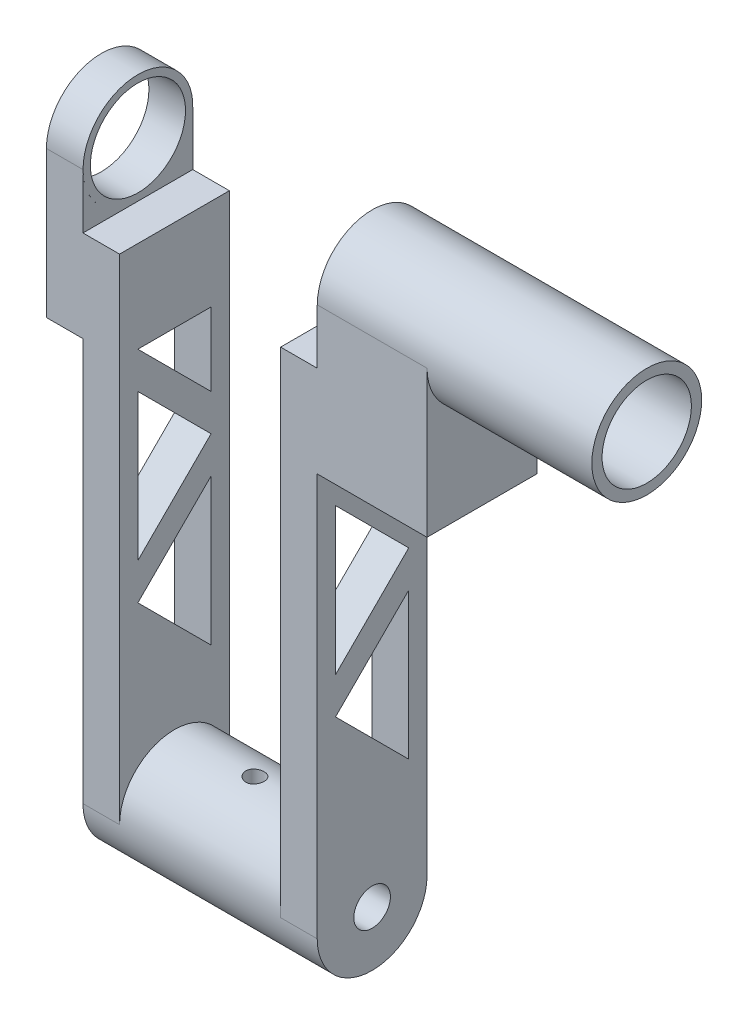
SolidWorks part; units mm, degrees
ref_plane "Alzado" through (0, 0, 0) normal (0, 0, 1) x (1, 0, 0)
ref_plane "Planta" through (0, 0, 0) normal (0, 1, 0) x (1, 0, 0)
ref_plane "Vista lateral" through (0, 0, 0) normal (1, 0, 0) x (0, 0, -1)
sketch "Croquis2" plane through (0, 0, 0) normal (1, 0, 0) x (0, 0, -1)
  line L0 (15, 0) -> (15, 150)
  line L1 (-15, 0) -> (-15, 150)
  line L2 (-15, 150) -> (15, 150) construction
  circle A0 centre (0, 0) radius 5
  arc A1 (-15, 0) -> (15, 0) centre (0, 0) ccw
  arc A2 (15, 150) -> (-15, 150) centre (0, 150) ccw
  circle A3 centre (0, 150) radius 5
extrude "Saliente-Extruir2" add sketch "Croquis2" along normal blind 64
shell "Vaciado1" thickness 10 removed face at (32, -7.5, 0) removed face at (32, 75, -15) removed face at (32, 75, 15)
sketch "Croquis3" plane through (0, 0, 0) normal (0, 1, 0) x (1, 0, 0)
  line L0 (32, 15) -> (32, -15) construction
  line L1 (54, 15) -> (10, 15) construction
  line L2 (10, -15) -> (54, -15) construction
  circle A0 centre (32, 0) radius 2.5
extrude "Cortar-Extruir1" cut sketch "Croquis3" against normal blind 36 and the other way blind 195
sketch "Croquis4" plane through (64, 0, 0) normal (1, 0, 0) x (0, 0, -1)
  line L0 (-15, 130) -> (-10, 130)
  line L1 (-15, 150) -> (-15, 0) construction
  line L2 (-15, 130) -> (15, 130)
  line L3 (15, 0) -> (15, 150) construction
  line L4 (15, 130) -> (10, 130)
  line L5 (10, 130) -> (10, 20)
  line L6 (-15, 20) -> (15, 20)
  line L7 (-15, 20) -> (-15, 130)
  line L8 (-15, 130) -> (15, 130)
  line L9 (15, 20) -> (15, 130)
  line L10 (-10, 130) -> (-10, 20)
  line L11 (10, 130) -> (-10, 110)
  line L12 (-10, 110) -> (10, 90)
extrude "Cortar-Extruir2" cut sketch "Croquis4" against normal blind 90 contours L11 L12 L5 region at (64, 110, -3.3333)
sketch "Croquis5" plane through (0, 0, 0) normal (-1, 0, 0) x (0, 0, 1)
  line L0 (-10, 90) -> (-10, 80)
  line L1 (-10, 80) -> (10, 100)
  line L2 (10, 100) -> (10, 60)
  line L3 (10, 60) -> (-10, 80)
extrude "Cortar-Extruir3" cut sketch "Croquis5" against normal blind 90 contours L3 L2 L1 region at (0, 80, 3.3333)
pattern_linear "MatrizL1" count 2 spacing 60 along (0, -1, 0) of "Cortar-Extruir2"
sketch "Croquis7" plane through (0, 0, 0) normal (-1, 0, 0) x (0, 0, 1)
  circle A0 centre (-0.0217, 149.9763) radius 13
  circle A2 centre (-0.0217, 149.9763) radius 15
extrude "Saliente-Extruir3" add sketch "Croquis7" along normal blind 10
sketch "Croquis8" plane through (64, 0, 0) normal (1, 0, 0) x (0, 0, -1)
  circle A0 centre (0.0217, 149.9763) radius 13
  circle A1 centre (0.0217, 149.9763) radius 15
extrude "Saliente-Extruir4" add sketch "Croquis8" along normal blind 10
sketch "Croquis9" plane through (74, 0, 0) normal (1, 0, 0) x (0, 0, -1)
  circle A0 centre (0.0217, 149.9763) radius 12.2
  circle A1 centre (0.0217, 149.9763) radius 15
extrude "Saliente-Extruir5" add sketch "Croquis9" along normal blind 65
sketch "Croquis11" plane through (0, 0, 0) normal (0, 0, 1) x (1, 0, 0)
  line L0 (29.5, 165) -> (0, 165) construction
  line L1 (0, 165) -> (64, 165)
  line L2 (0, 165) -> (0, 135)
  line L3 (0, 135) -> (64, 135)
  line L4 (64, 165) -> (64, 135)
  line L5 (64, 150) -> (64, 0) construction
  line L6 (64, 135) -> (139, 135) construction
extrude "Cortar-Extruir4" cut sketch "Croquis11" against normal blind 65 and the other way blind 65
sketch "Croquis12" plane through (64, 0, 0) normal (1, 0, 0) x (0, 0, -1)
  line L0 (15, 0) -> (15, 135) construction
  line L2 (-15, 135) -> (-15, 110)
  line L3 (-15, 110) -> (15, 110)
  line L4 (15, 135) -> (15, 110)
  line L5 (-15, 135) -> (-15, 150)
  line L6 (15, 135) -> (15, 150)
  arc A0 (-15, 150) -> (15, 150) centre (0, 150) ccw
extrude "Saliente-Extruir6" add sketch "Croquis12" along normal blind 30
sketch "Croquis13" plane through (0, 0, 0) normal (-1, 0, 0) x (0, 0, 1)
  line L0 (-15, 135) -> (-15, 150)
  line L2 (-15, 135) -> (-15, 110)
  line L3 (-15, 110) -> (15, 110)
  line L4 (15, 135) -> (15, 110)
  line L5 (15, 135) -> (15, 150)
  arc A0 (-15, 150) -> (15, 150) centre (0, 150) ccw
extrude "Saliente-Extruir7" add sketch "Croquis13" along normal blind 10
sketch "Croquis14" plane through (10, 0, 0) normal (1, 0, 0) x (0, 0, -1)
  line L0 (-10, 110) -> (10, 130)
  line L1 (10, 130) -> (10, 110)
  line L2 (10, 130) -> (10, 90) construction
  line L3 (10, 110) -> (-10, 110)
extrude "Saliente-Extruir8" add sketch "Croquis14" against normal blind 10
sketch "Croquis15" plane through (54, 0, 0) normal (-1, 0, 0) x (0, 0, 1)
  line L0 (-10, 130) -> (10, 110)
  line L1 (10, 110) -> (-10, 110)
  line L2 (-10, 130) -> (-10, 90) construction
  line L3 (-10, 110) -> (-10, 130)
extrude "Saliente-Extruir9" add sketch "Croquis15" against normal blind 10
